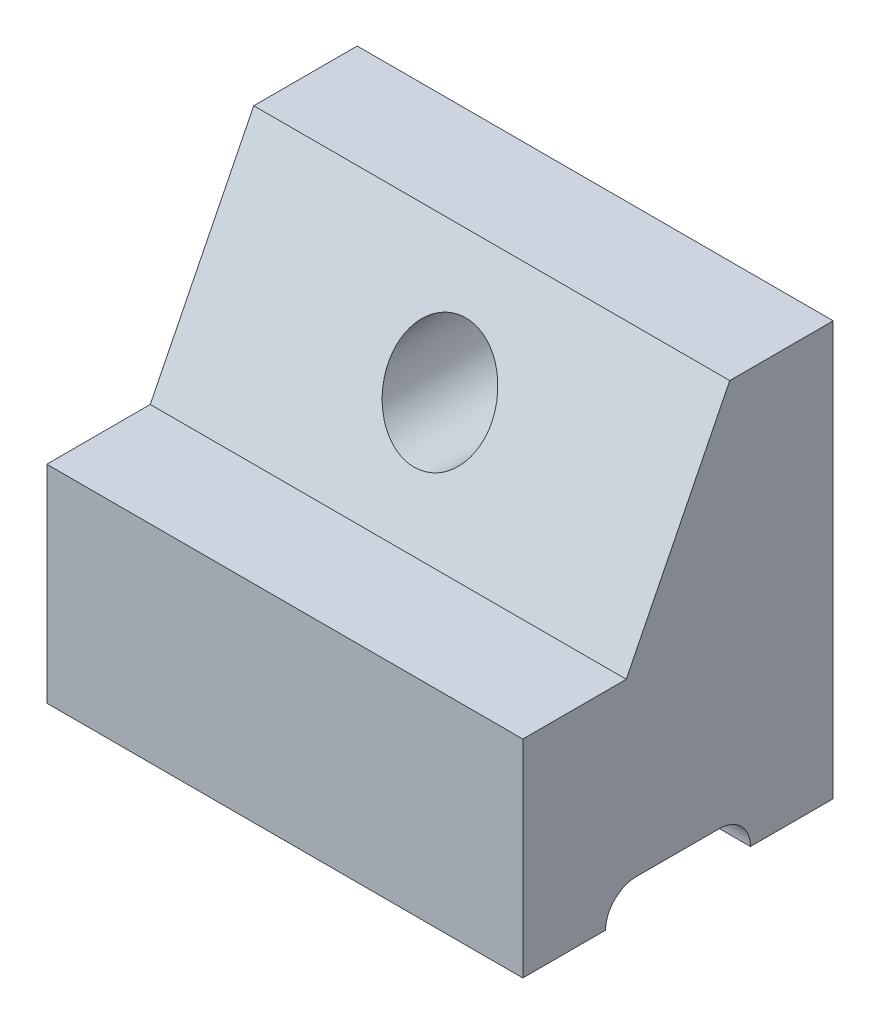
SolidWorks part; units mm, degrees
ref_plane "前基準面" through (0, 0, 0) normal (0, 0, 1) x (1, 0, 0)
ref_plane "上基準面" through (0, 0, 0) normal (0, 1, 0) x (1, 0, 0)
ref_plane "右基準面" through (0, 0, 0) normal (1, 0, 0) x (0, 0, -1)
sketch "草圖1" plane through (0, 0, 0) normal (0, 0, 1) x (1, 0, 0)
  line L1 (-23, 20) -> (23, 20)
  line L2 (-23, 20) -> (-23, -20)
  line L3 (-23, -20) -> (23, -20)
  line L4 (23, 20) -> (23, -20)
  line L5 (-23, 20) -> (23, -20) construction
  line L6 (-23, -20) -> (23, 20) construction
  point P0 (0, 0)
  dimension "D1" = 40
  dimension "D2" = 46
extrude "填料-伸長1" add sketch "草圖1" along normal mid plane 30 contours L2 L3 L4 L1
sketch "草圖2" plane through (0, 0, 15) normal (0, 0, 1) x (1, 0, 0)
  line L0 (-23, 20) -> (23, 20) construction
  line L1 (-23, 20) -> (-23, -20) construction
  circle A0 centre (0, 10) radius 5
  point P4 (0, 0)
  point P6 (-66.505, 43.0628)
  dimension "D3" = 10
  dimension "D1" = 10
  dimension "D2" = 23
extrude "除料-伸長1" cut sketch "草圖2" against normal through all
sketch "草圖4" plane through (23, 0, 0) normal (1, 0, 0) x (0, 0, -1)
  line L0 (-15, -20) -> (15, -20) construction
  line L1 (-15, 20) -> (5, 20)
  line L2 (-15, 20) -> (-15, 0)
  line L5 (-7, -20) -> (7, -20)
  line L6 (-7, -20) -> (-7, -17)
  line L7 (-7, -17) -> (7, -17)
  line L8 (7, -20) -> (7, -17)
  line M12 (-15, -20) -> (15, -20)
  dimension "D3" = 8
  dimension "D4" = 14
  dimension "D5" = 3
extrude "除料-伸長2" cut sketch "草圖4" against normal through all contours L8 L7 L6 M12 region at (23, -18.5, 0)
fillet "圓角3" radius 3 1 edges at (0, -17, 7)
fillet "圓角8" radius 3 1 edges at (0, -17, -7)
sketch "草圖5" plane through (23, 0, 0) normal (1, 0, 0) x (0, 0, -1)
  line L0 (5, 20) -> (-5, 0)
  line L1 (-15, 20) -> (5, 20)
  line L2 (-15, 20) -> (-15, 0)
  line L3 (-15, 0) -> (5, 0)
  line L4 (5, 20.1809) -> (5, 0)
  line L5 (-15, 20) -> (-5, 20)
  line L6 (-15, 20) -> (-15, 0)
  line L7 (-15, 0) -> (-5, 0)
  point P5 (0, 0)
  point P8 (0, 0)
  point P9 (0, 0)
  line M16 (15, 20) -> (-15, 20)
  line M17 (-15, 20) -> (-15, -20)
  dimension "D1" = 20
  dimension "D2" = 20
extrude "除料-伸長3" cut sketch "草圖5" against normal through all contours L3 L0 L1 M17 M16 region at (23, 11.1111, 7.2222)
equation "\"mm\"=5"
